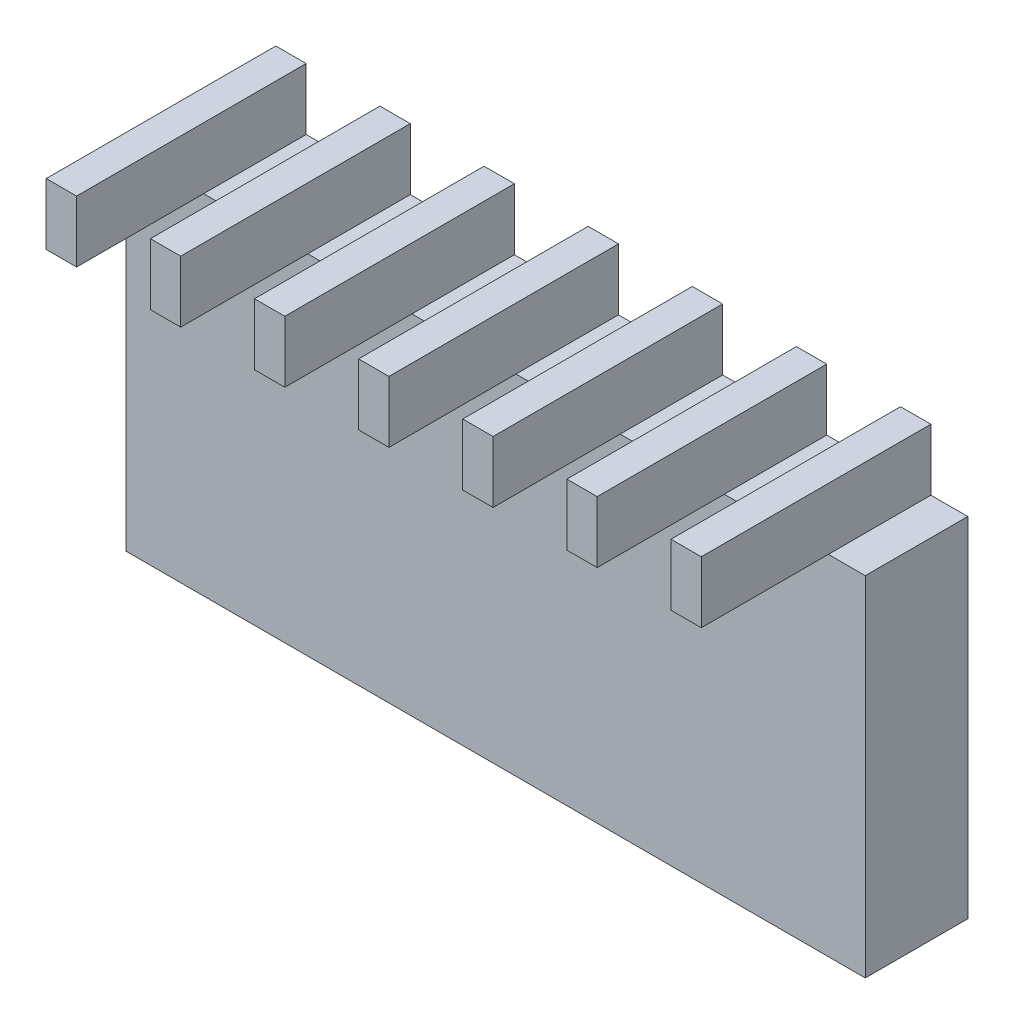
SolidWorks part; units mm, degrees
ref_plane "前视基准面" through (0, 0, 0) normal (0, 0, 1) x (1, 0, 0)
ref_plane "上视基准面" through (0, 0, 0) normal (0, 1, 0) x (1, 0, 0)
ref_plane "右视基准面" through (0, 0, 0) normal (1, 0, 0) x (0, 0, -1)
other "Configuration Table"
sketch "草图1" plane through (0, 0, 0) normal (0, 0, 1) x (1, 0, 0)
  line L0 (7.3822, -4.2023) -> (7.3822, 4.2977) construction
  line L1 (-5.5678, 4.2977) -> (20.3322, 4.2977)
  line L2 (-5.5678, 4.2977) -> (-5.5678, -4.2023)
  line L3 (-5.5678, -4.2023) -> (20.3322, -4.2023)
  line L4 (20.3322, 4.2977) -> (20.3322, -4.2023)
  line L5 (-4.4178, 5.7977) -> (19.1822, 5.7977)
  line L6 (-4.4178, 5.7977) -> (-4.4178, 4.2977)
  line L7 (-4.4178, 4.2977) -> (19.1822, 4.2977)
  line L8 (19.1822, 5.7977) -> (19.1822, 4.2977)
  dimension "D1" = 8.5
  dimension "D2" = 25.9
  dimension "D3" = 23.6
  dimension "D4" = 10
  dimension "D5" = 1.15
extrude "凸台-拉伸1" add sketch "草图1" along normal blind 2.5 contours L3 L4 L1 L2
extrude "凸台-拉伸2" add sketch "草图1<5>" along normal blind 2.5 contours L5 L8 L7 L6
sketch "草图1<5>" plane through (0, 0, 0) normal (0, 0, 1) x (1, 0, 0) same geometry as "草图1"
sketch "草图2" plane through (0, 0, 2.5) normal (0, 0, 1) x (1, 0, 0)
  line L0 (-4.4178, 4.2977) -> (19.1822, 4.2977)
  line L1 (-4.4178, 5.7977) -> (-4.4178, 4.2977) construction
  line L2 (-4.4178, 5.7977) -> (19.1822, 5.7977) construction
  line L3 (19.1822, 5.7977) -> (19.1822, 4.2977) construction
  line L4 (19.1822, 5.7977) -> (19.1822, 4.2977)
  line L5 (-4.4178, 5.7977) -> (19.1822, 5.7977)
  line L6 (-4.4178, 5.7977) -> (-4.4178, 4.2977)
extrude "凸台-拉伸3" add sketch "草图2" along normal blind 3.1
sketch "草图3" plane through (0, 5.7977, 0) normal (0, 1, 0) x (1, 0, 0)
  line L0 (19.1822, -5.6) -> (-4.4178, -5.6) construction
  line L1 (16.6422, 0) -> (18.4422, 0)
  line L2 (16.6422, 0) -> (16.6422, -5.6)
  line L3 (16.6422, -5.6) -> (18.4422, -5.6)
  line L4 (18.4422, 0) -> (18.4422, -5.6)
  line L5 (19.1822, -5.6) -> (19.1822, 0) construction
  line L6 (14.1022, 0) -> (14.1022, -5.6)
  line L7 (14.1022, 0) -> (15.9022, 0)
  line L8 (15.9022, 0) -> (15.9022, -5.6)
  line L9 (14.1022, -5.6) -> (15.9022, -5.6)
  line L10 (11.5622, 0) -> (11.5622, -5.6)
  line L11 (11.5622, 0) -> (13.3622, 0)
  line L12 (13.3622, 0) -> (13.3622, -5.6)
  line L13 (11.5622, -5.6) -> (13.3622, -5.6)
  line L14 (9.0222, 0) -> (9.0222, -5.6)
  line L15 (9.0222, 0) -> (10.8222, 0)
  line L16 (10.8222, 0) -> (10.8222, -5.6)
  line L17 (9.0222, -5.6) -> (10.8222, -5.6)
  line L18 (6.4822, 0) -> (6.4822, -5.6)
  line L19 (6.4822, 0) -> (8.2822, 0)
  line L20 (8.2822, 0) -> (8.2822, -5.6)
  line L21 (6.4822, -5.6) -> (8.2822, -5.6)
  line L22 (3.9422, 0) -> (3.9422, -5.6)
  line L23 (3.9422, 0) -> (5.7422, 0)
  line L24 (5.7422, 0) -> (5.7422, -5.6)
  line L25 (3.9422, -5.6) -> (5.7422, -5.6)
  line L26 (1.4022, 0) -> (1.4022, -5.6)
  line L27 (1.4022, 0) -> (3.2022, 0)
  line L28 (3.2022, 0) -> (3.2022, -5.6)
  line L29 (1.4022, -5.6) -> (3.2022, -5.6)
  line L30 (-1.1378, 0) -> (-1.1378, -5.6)
  line L31 (-1.1378, 0) -> (0.6622, 0)
  line L32 (0.6622, 0) -> (0.6622, -5.6)
  line L33 (-1.1378, -5.6) -> (0.6622, -5.6)
  line L34 (-3.6778, 0) -> (-3.6778, -5.6)
  line L35 (-3.6778, 0) -> (-1.8778, 0)
  line L36 (-1.8778, 0) -> (-1.8778, -5.6)
  line L37 (-3.6778, -5.6) -> (-1.8778, -5.6)
  line L38 (-4.4178, 0) -> (19.1822, 0) construction
  point P8 (-4.0478, 0)
  dimension "D1" = 1.8
  dimension "D2" = 0.74
  dimension "D4" = 0.37
  dimension "D3" = 9
extrude "切除-拉伸1" cut sketch "草图3" against normal blind 1.5
sketch "草图4" plane through (0, 4.2977, 0) normal (0, 1, 0) x (1, 0, 0)
  line L0 (13.3622, -2.5) -> (13.3622, 0) construction
  line L1 (12.4622, 1.4866) -> (21.2321, 1.4866)
  line L2 (12.4622, 1.4866) -> (12.4622, -6.2433)
  line L3 (12.4622, -6.2433) -> (21.2321, -6.2433)
  line L4 (21.2321, 1.4866) -> (21.2321, -6.2433)
  dimension "D1" = 0.9
extrude "切除-拉伸2" cut sketch "草图4" against normal blind 10 and the other way blind 2
sketch "草图5" plane through (0, 0, 0) normal (0, 0, -1) x (-1, 0, 0)
  line L0 (4.0478, 5.7977) -> (4.0478, -4.2023) construction
  line L3 (5.5678, 4.2977) -> (5.5678, -4.2023) construction
  dimension "D1" = 1.52
sketch "草图6" plane through (0, -4.2023, 0) normal (0, -1, 0) x (1, 0, 0)
  line L0 (-4.0478, 2.5) -> (-4.0478, 0)
  line L1 (-4.4178, 2.5) -> (-3.6778, 2.5) construction
sketch "草图7" plane through (0, -4.2023, 0) normal (0, -1, 0) x (1, 0, 0)
  line L6 (-5.5678, 1.25) -> (1.4206, 1.25) construction
  line L8 (-4.0478, 2.5) -> (-4.0478, 0) construction
  line L9 (-4.8723, 1.9913) -> (-3.2233, 1.9913)
  line L10 (-4.8723, 1.9913) -> (-4.8723, 0.5087)
  line L11 (-4.8723, 0.5087) -> (-3.2233, 0.5087)
  line L12 (-3.2233, 1.9913) -> (-3.2233, 0.5087)
  line L13 (-4.8723, 1.9913) -> (-3.2233, 0.5087) construction
  line L14 (-4.8723, 0.5087) -> (-3.2233, 1.9913) construction
  point P0 (-4.0478, 1.25)
